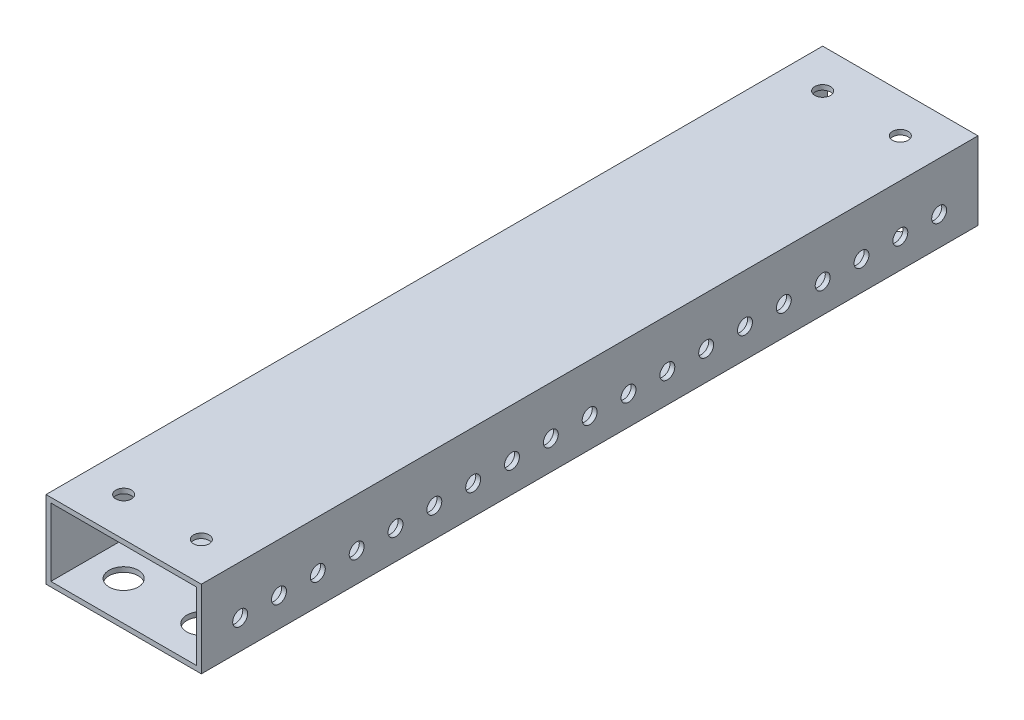
SolidWorks part; units mm, degrees
other "Markup1"
sketch "Sketch7" plane through (25.4, 12.7, -127) normal (0.9965, 0.0171, -0.0817) x (-0.082, 0.0128, -0.9966)
ref_plane "Front Plane" through (0, 0, 0) normal (0, 0, 1) x (1, 0, 0)
ref_plane "Top Plane" through (0, 0, 0) normal (0, 1, 0) x (1, 0, 0)
ref_plane "Right Plane" through (0, 0, 0) normal (1, 0, 0) x (0, 0, -1)
sketch "Sketch1" plane through (0, 0, 0) normal (0, 0, 1) x (1, 0, 0)
  line L0 (-23.8125, 11.1125) -> (23.8125, 11.1125)
  line L1 (-25.4, -12.7) -> (25.4, -12.7)
  line L2 (-25.4, -12.7) -> (-25.4, 12.7)
  line L3 (-25.4, 12.7) -> (25.4, 12.7)
  line L4 (25.4, -12.7) -> (25.4, 12.7)
  line L5 (-25.4, -12.7) -> (25.4, 12.7) construction
  line L6 (-25.4, 12.7) -> (25.4, -12.7) construction
  line L7 (23.8125, -11.1125) -> (23.8125, 11.1125)
  line L8 (-23.8125, -11.1125) -> (23.8125, -11.1125)
  line L9 (-23.8125, -11.1125) -> (-23.8125, 11.1125)
  point P0 (0, 0)
  dimension "D1" = 50.8
  dimension "D2" = 25.4
  dimension "D3" = 1.5875
extrude "Boss-Extrude1" add sketch "Sketch1" along normal mid plane 254
sketch "Sketch3" plane through (0, 12.7, 0) normal (0, 1, 0) x (1, 0, 0)
  line L0 (25.4, 127) -> (-25.4, 127) construction
  line L1 (25.4, -127) -> (-25.4, -127) construction
  line L3 (-25.4, -127) -> (-25.4, 127) construction
  line L4 (25.4, -127) -> (25.4, 127) construction
  circle A0 centre (-12.7, -114.3) radius 2.5527
  circle A1 centre (12.7, -114.3) radius 2.5527
  circle A2 centre (-12.7, 114.3) radius 2.5527
  circle A3 centre (12.7, 114.3) radius 2.5527
  dimension "D5" = 5.1054
  dimension "D1" = 12.7
  dimension "D2" = 12.7
  dimension "D3" = 12.7
  dimension "D4" = 12.7
  dimension "D6" = 25.4
  dimension "D7" = 25.4
  dimension "D8" = 12.7
  dimension "D9" = 12.7
  dimension "D10" = 12.7
  dimension "D11" = 12.7
extrude "Cut-Extrude1" cut sketch "Sketch3" against normal up to surface (1.5875 mm away) up to face at (0, 11.1125, 0)
sketch "Sketch5" plane through (0, -12.7, 0) normal (0, -1, 0) x (1, 0, 0)
  circle A0 centre (-12.7, -114.3) radius 2.5527 construction
  circle A1 centre (12.7, -114.3) radius 2.5527 construction
  circle A2 centre (12.7, 114.3) radius 2.5527 construction
  circle A3 centre (-12.7, 114.3) radius 2.5527 construction
  circle A4 centre (-12.7, -114.3) radius 2.5527
  circle A5 centre (12.7, -114.3) radius 2.5527
  circle A6 centre (12.7, 114.3) radius 2.5527
  circle A7 centre (-12.7, 114.3) radius 2.5527
  circle A8 centre (-12.7, 114.3) radius 4.7625
  circle A9 centre (12.7, 114.3) radius 4.7625
  circle A10 centre (12.7, -114.3) radius 4.7625
  circle A11 centre (-12.7, -114.3) radius 4.7625
  dimension "D1" = 9.525
extrude "Cut-Extrude2" cut sketch "Sketch5" against normal up to surface (1.5875 mm away) contours A10 A5 | A5 | A11 A4 | A4 | A6 | A9 A6 | A8 A7 | A7 region at (-12.7, -12.7, -114.3) region at (12.7, -12.7, -114.3) region at (12.7, -12.7, 114.3) region at (-12.7, -12.7, 114.3) region at (-17.3278, -12.7, 114.3) region at (8.0722, -12.7, 114.3) region at (8.0722, -12.7, -114.3) region at (-17.3278, -12.7, -114.3) up to face at (0, -11.1125, 0)
sketch "Sketch6" plane through (25.4, 0, 0) normal (1, 0, 0) x (0, 0, -1)
  line L0 (-127, -12.7) -> (-127, 12.7) construction
  line L1 (-127, -12.7) -> (127, -12.7) construction
  line L2 (0, 12.7) -> (0, -12.7) construction
  line L3 (-127, 12.7) -> (127, 12.7) construction
  circle A0 centre (-114.3, -3.175) radius 2.4384
  circle A1 centre (-101.6, -3.175) radius 2.4384
  circle A2 centre (-88.9, -3.175) radius 2.4384
  circle A3 centre (88.9, -3.175) radius 2.4384
  circle A4 centre (101.6, -3.175) radius 2.4384
  circle A5 centre (114.3, -3.175) radius 2.4384
  circle A6 centre (-76.2, -3.175) radius 2.4384
  circle A7 centre (-63.5, -3.175) radius 2.4384
  circle A8 centre (-50.8, -3.175) radius 2.4384
  circle A9 centre (-38.1, -3.175) radius 2.4384
  circle A10 centre (-25.4, -3.175) radius 2.4384
  circle A11 centre (-12.7, -3.175) radius 2.4384
  circle A12 centre (0, -3.175) radius 2.4384
  circle A13 centre (12.7, -3.175) radius 2.4384
  circle A14 centre (25.4, -3.175) radius 2.4384
  circle A15 centre (38.1, -3.175) radius 2.4384
  circle A16 centre (50.8, -3.175) radius 2.4384
  circle A17 centre (63.5, -3.175) radius 2.4384
  circle A18 centre (76.2, -3.175) radius 2.4384
  dimension "D1" = 4.8768
  dimension "D7" = 4.8768
  dimension "D2" = 12.7
  dimension "D3" = 9.525
  dimension "D4" = 12.7
  dimension "D5" = 12.7
  dimension "D6" = 12.7
  dimension "D8" = 9.525
  dimension "D10" = 12.7
  dimension "D9" = 13
extrude "Cut-Extrude3" cut sketch "Sketch6" against normal up to surface (1.5875 mm away) contours A5 | A4 | A3 | A0 | A1 | A2 | A6 | A7 | A8 | A9 | A10 | A11 | A12 L2 | L2 A12 | A13 | A14 | A15 | A16 | A17 | A18 | A12 region at (25.4, -3.175, -1.0349) region at (25.4, -3.175, 1.0349) region at (25.4, -3.175, 114.3) region at (25.4, -3.175, 101.6) region at (25.4, -3.175, 88.9) region at (25.4, -3.175, -88.9) region at (25.4, -3.175, -101.6) region at (25.4, -3.175, -114.3) region at (25.4, -3.175, 76.2) region at (25.4, -3.175, 63.5) region at (25.4, -3.175, 50.8) region at (25.4, -3.175, 38.1) region at (25.4, -3.175, 25.4) region at (25.4, -3.175, 12.7) region at (25.4, -3.175, -12.7) region at (25.4, -3.175, -25.4) region at (25.4, -3.175, -38.1) region at (25.4, -3.175, -50.8) region at (25.4, -3.175, -63.5) region at (25.4, -3.175, -76.2) up to face at (23.8125, 0, 0)
